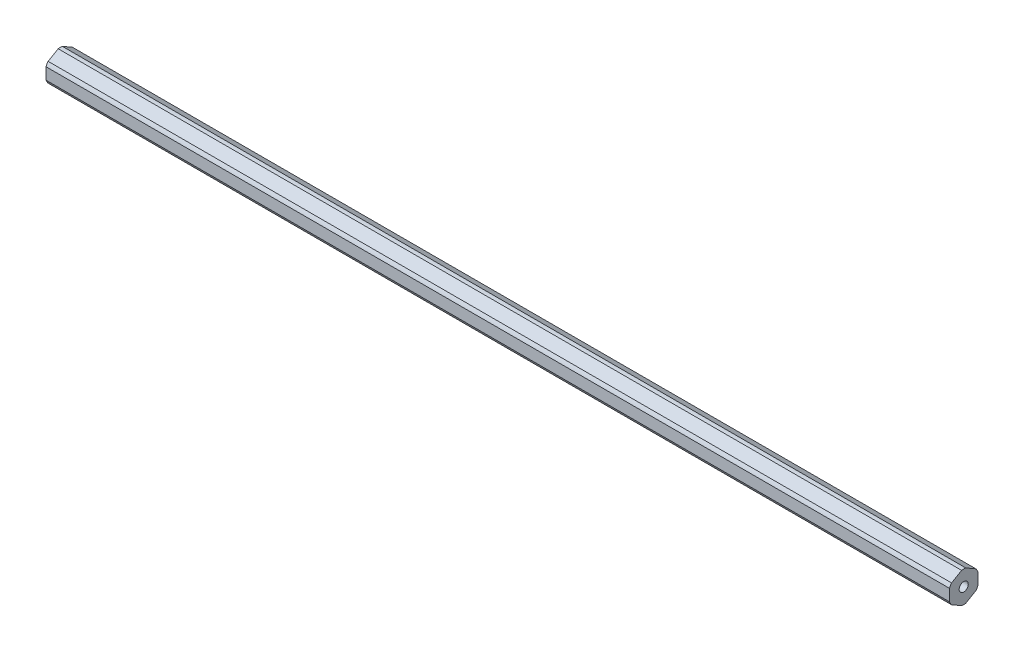
SolidWorks part; units mm, degrees
material "7075-T6 (SN)"
ref_plane "Front Plane" through (0, 0, 0) normal (0, 0, 1) x (1, 0, 0)
ref_plane "Top Plane" through (0, 0, 0) normal (0, 1, 0) x (1, 0, 0)
ref_plane "Right Plane" through (0, 0, 0) normal (1, 0, 0) x (0, 0, -1)
sketch "Sketch1" plane through (0, 0, 0) normal (1, 0, 0) x (0, 0, -1)
  line L1 (0, 7.3323) -> (-6.35, 3.6662)
  line L2 (-6.35, 3.6662) -> (-6.35, -3.6662)
  line L3 (-6.35, -3.6662) -> (0, -7.3323)
  line L4 (0, -7.3323) -> (6.35, -3.6662)
  line L5 (6.35, -3.6662) -> (6.35, 3.6662)
  line L6 (6.35, 3.6662) -> (0, 7.3323)
  circle A1 centre (0, 0) radius 6.858
  circle A2 centre (0, 0) radius 6.35 construction
  dimension "D1" = 13.716
  dimension "D2" = 12.7
extrude "Boss-Extrude1" add sketch "Sketch1" along normal mid plane 401.6375 contours L5 A1 L6 L1 L2 L3 L4 region at (0, 0, 0)
sketch "Sketch3" plane through (-200.8187, 0, 0) normal (-1, 0, 0) x (0, 0, 1)
  circle A0 centre (0, 0) radius 6.35
  dimension "D1" = 12.7
hole_wizard "#10-32 Tapped Hole1" positions "3DSketch1" profile "Sketch4" tap size "#10-32" standard "ANSI Inch"
sketch3d "3DSketch1"
  line L0 (200.8187, 0, 0) -> (-200.8187, 0, 0) construction
  point P0 (-200.8187, 0, 0)
  point P3 (200.8187, 0, 0)
sketch "Sketch4" plane through (-200.8187, 0, 0) normal (0, 1, 0) x (0, 0, 1)
  line L0 (0, 0) -> (0, 17.5608)
  line L1 (0, 17.5608) -> (2.0193, 16.3474)
  line L2 (2.0193, 16.3474) -> (2.0193, 0)
  line L5 (2.0193, 0) -> (0, 0)
  line L10 (0, 17.5608) -> (-2.0193, 16.3474) construction
  line L11 (0, -6.35) -> (0, 107.95) construction
  dimension "Tap Drill Dia." = 4.0386
  dimension "Tap Drill Depth" = 16.3474
  dimension "Drill Angle" = 118
cosmetic thread "Hole Thread1" parameters "D1"=13.97, "D2"=4.826
cosmetic thread "Hole Thread2" parameters "D1"=13.97, "D2"=4.826
